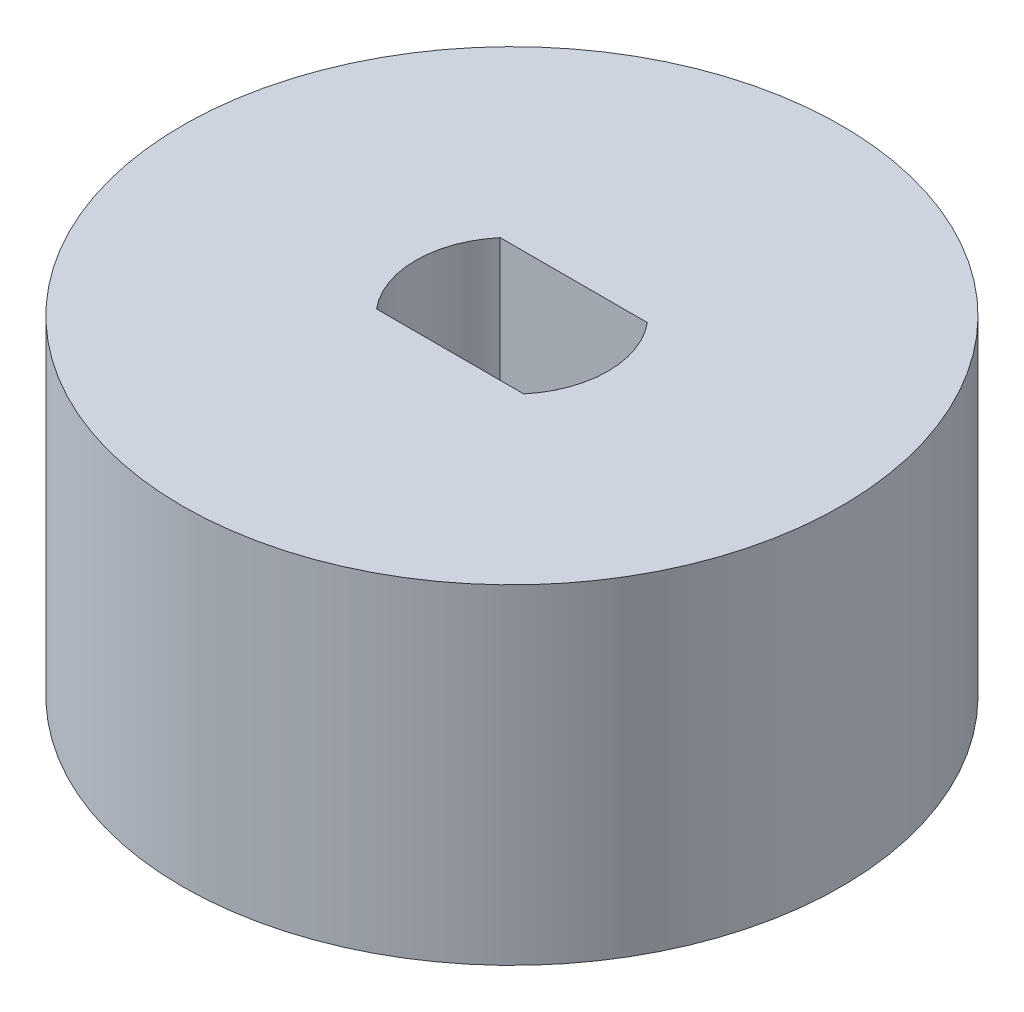
SolidWorks part; units mm, degrees
ref_plane "Front Plane" through (0, 0, 0) normal (0, 0, 1) x (1, 0, 0)
ref_plane "Top Plane" through (0, 0, 0) normal (0, 1, 0) x (1, 0, 0)
ref_plane "Right Plane" through (0, 0, 0) normal (1, 0, 0) x (0, 0, -1)
sketch "Sketch1" plane through (0, 0, 0) normal (0, 1, 0) x (1, 0, 0)
  line L1 (-2.6795, 2.25) -> (2.6795, 2.25)
  line L3 (-2.6795, -2.25) -> (2.6795, -2.25)
  arc A0 (-2.6795, 2.25) -> (-2.6795, -2.25) centre (0, 0) ccw
  arc A1 (2.6795, -2.25) -> (2.6795, 2.25) centre (0, 0) ccw
  circle A2 centre (0, 0) radius 12
extrude "Boss-Extrude1" add sketch "Sketch1" along normal blind 12
